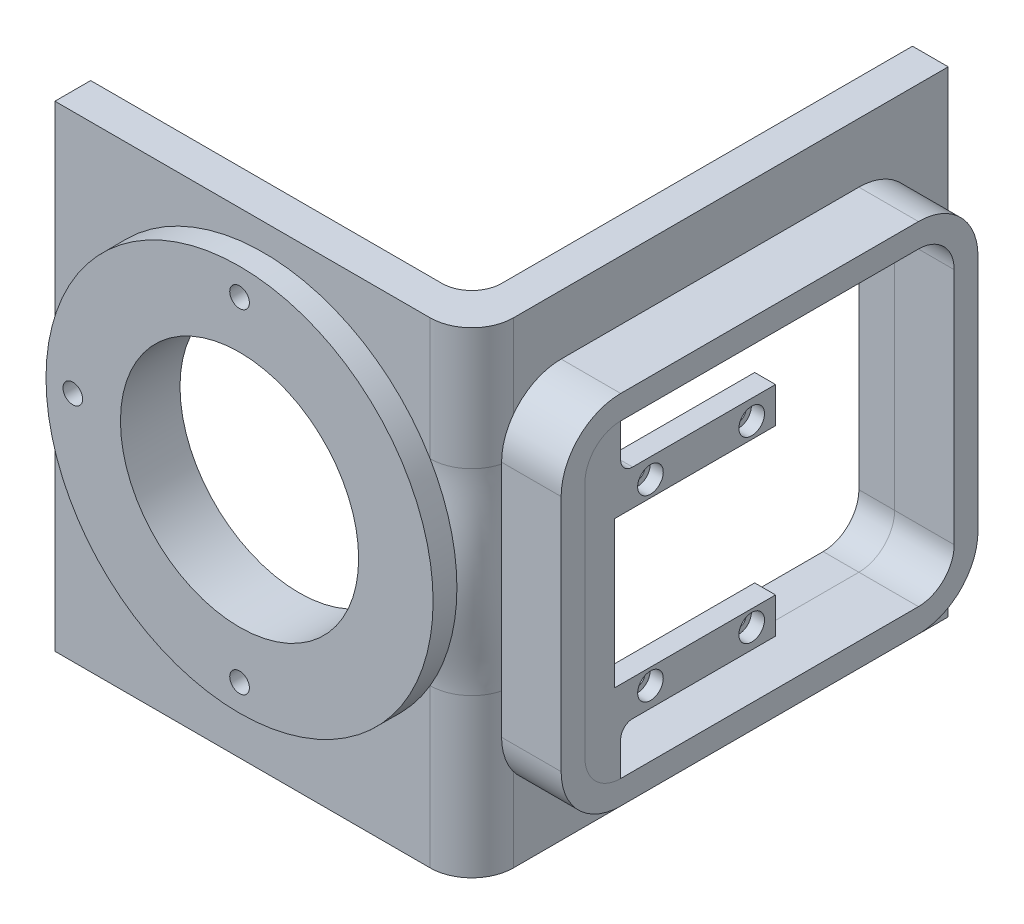
SolidWorks part; units mm, degrees
ref_plane "Front Plane" through (0, 0, 0) normal (0, 0, 1) x (1, 0, 0)
ref_plane "Top Plane" through (0, 0, 0) normal (0, 1, 0) x (1, 0, 0)
ref_plane "Right Plane" through (0, 0, 0) normal (1, 0, 0) x (0, 0, -1)
sketch "Sketch1" plane through (0, 0, 0) normal (0, 0, 1) x (1, 0, 0)
  circle A5 centre (0, 0) radius 32.5
  dimension "D1" = 65
extrude "Boss-Extrude1" add sketch "Sketch1" against normal blind 4
ref_plane "Plane1" through (45, 0, 0) normal (1, 0, 0) x (0, 0, -1)
sketch "Sketch10" plane through (0, 0, -4) normal (0, 0, -1) x (-1, 0, 0)
  line L0 (0, -3) -> (0, 0) construction
  line L1 (-35, -43) -> (35, -43)
  line L2 (-35, -43) -> (-35, 37)
  line L3 (-35, 37) -> (35, 37)
  line L4 (35, -43) -> (35, 37)
  line L5 (-35, -43) -> (35, 37) construction
  line L6 (-35, 37) -> (35, -43) construction
  point P0 (0, -3)
  dimension "D3" = 3
  dimension "D1" = 80
  dimension "D2" = 70
extrude "Boss-Extrude6" add sketch "Sketch10" along normal blind 80
sketch "Sketch2" plane through (45, 0, 0) normal (1, 0, 0) x (0, 0, -1)
  line L2 (0, -3) -> (146.6861, -3) construction
  line L3 (44, -3) -> (44, 30) construction
  line L5 (4, 37) -> (4, -43) construction
  line L6 (84, 37) -> (84, -43) construction
  line L7 (19, -33) -> (69, -33)
  line L8 (9, -23) -> (9, 17)
  line L9 (19, 27) -> (69, 27)
  line L10 (79, -23) -> (79, 17)
  line L11 (9, -33) -> (79, 27) construction
  line L12 (9, 27) -> (79, -33) construction
  arc A1 (19, -33) -> (9, -23) centre (19, -23) cw
  arc A2 (69, -33) -> (79, -23) centre (69, -23) ccw
  arc A3 (69, 27) -> (79, 17) centre (69, 17) cw
  arc A4 (9, 17) -> (19, 27) centre (19, 17) cw
  point P0 (84, -3)
  dimension "D1" = 70
  dimension "D3" = 10
  dimension "D2" = 60
extrude "Boss-Extrude2" add sketch "Sketch2" against normal up to surface (10 mm away) separate body up to face at (35, -3, -44)
sketch "Sketch11" plane through (0, 37, 0) normal (0, 1, 0) x (1, 0, 0)
  line L1 (-35, 84) -> (29, 84)
  line L2 (-35, 84) -> (-35, 10)
  line L3 (-35, 10) -> (29, 10)
  line L4 (29, 84) -> (29, 10)
  dimension "D1" = 74
  dimension "D2" = 64
extrude "Cut-Extrude5" cut sketch "Sketch11" against normal through all
sketch "Sketch4" plane through (35, 0, 0) normal (-1, 0, 0) x (0, 0, 1)
  line L8 (-69, -29) -> (-19, -29)
  line L9 (-75, 17) -> (-75, -23)
  line L10 (-19, 23) -> (-69, 23)
  line L11 (-13, -23) -> (-13, 17)
  line L12 (-69, -29) -> (-19, -29)
  line L13 (-75, 17) -> (-75, -23)
  line L14 (-19, 23) -> (-69, 23)
  line L15 (-13, -23) -> (-13, 17)
  arc A10 (-75, -23) -> (-69, -29) centre (-69, -23) ccw
  arc A11 (-69, 23) -> (-75, 17) centre (-69, 17) ccw
  arc A12 (-13, 17) -> (-19, 23) centre (-19, 17) ccw
  arc A13 (-19, -29) -> (-13, -23) centre (-19, -23) ccw
  arc A14 (-75, -23) -> (-69, -29) centre (-69, -23) ccw
  arc A15 (-69, 23) -> (-75, 17) centre (-69, 17) ccw
  arc A16 (-13, 17) -> (-19, 23) centre (-19, 17) ccw
  arc A17 (-19, -29) -> (-13, -23) centre (-19, -23) ccw
  dimension "D1" = 4
extrude "Cut-Extrude2" cut sketch "Sketch4" against normal through all contours L12 A17 L15 A16 L14 A15 L13 A14 region at (35, -3, -44)
sketch "Sketch5" plane through (45, 0, 0) normal (1, 0, 0) x (0, 0, -1)
  line L0 (48, -3) -> (13, -3) construction
  line L1 (45, 15.3) -> (45, 9.3)
  line L2 (45, 9.3) -> (18, 9.3)
  line L3 (18, 9.3) -> (18, -15.3)
  line L4 (18, -15.3) -> (45, -15.3)
  line L5 (45, -15.3) -> (45, -21.3)
  line L6 (45, -21.3) -> (19, -21.3)
  line L8 (45, 15.3) -> (19, 15.3)
  line L10 (48, -3) -> (48, -18) construction
  line L11 (48, -18) -> (41, -18) construction
  line L12 (41, -18) -> (39, -18) construction
  line L13 (39, -18) -> (24, -18) construction
  line L15 (13, 17) -> (13, -23)
  line L16 (19, 15.3) -> (19, 23)
  line L17 (19, -21.3) -> (19, -29)
  line L18 (13, -23) -> (13, 17) construction
  circle A0 centre (48, -3) radius 11 construction
  arc A1 (19, 23) -> (13, 17) centre (19, 17) ccw construction
  circle A2 centre (41, -18) radius 1.25
  arc A3 (19, 23) -> (13, 17) centre (19, 17) ccw
  circle A6 centre (24, -18) radius 1.25
  circle A7 centre (41, 12) radius 1.25
  circle A9 centre (24, 12) radius 1.25
  arc A10 (13, -23) -> (19, -29) centre (19, -23) ccw
  point P8 (18, -3)
  dimension "D1" = 22
  dimension "D6" = 2.5
  dimension "D3" = 24.6
  dimension "D4" = 15
  dimension "D5" = 7
  dimension "D7" = 17
  dimension "D9" = 6
  dimension "D10" = 5
  dimension "D12" = 3
  dimension "D2" = 30
extrude "Boss-Extrude3" add sketch "Sketch5" against normal blind 3.5
sketch "Sketch13" plane through (35, 0, 0) normal (1, 0, 0) x (0, 0, -1)
  line L4 (13, 17) -> (13, -23)
  line L5 (19, -29) -> (69, -29)
  line L6 (75, -23) -> (75, 17)
  line L7 (69, 23) -> (19, 23)
  line L8 (13, 17) -> (13, -23)
  line L9 (19, -29) -> (69, -29)
  line L10 (75, -23) -> (75, 17)
  line L11 (69, 23) -> (19, 23)
  arc A6 (19, 23) -> (13, 17) centre (19, 17) ccw
  arc A7 (13, -23) -> (19, -29) centre (19, -23) ccw
  arc A8 (69, -29) -> (75, -23) centre (69, -23) ccw
  arc A9 (75, 17) -> (69, 23) centre (69, 17) ccw
  arc A10 (19, 23) -> (13, 17) centre (19, 17) ccw
  arc A11 (13, -23) -> (19, -29) centre (19, -23) ccw
  arc A12 (69, -29) -> (75, -23) centre (69, -23) ccw
  arc A13 (75, 17) -> (69, 23) centre (69, 17) ccw
  dimension "D1" = 0
extrude "Cut-Extrude6" cut sketch "Sketch13" against normal up to surface (6 mm away) up to face at (29, -3, -47)
sketch "Sketch14" plane through (0, 0, 0) normal (0, 0, 1) x (1, 0, 0)
  circle A2 centre (0, 0) radius 28.5
  circle A3 centre (0, 0) radius 28.5
  dimension "D1" = 4
sketch "Sketch16" plane through (45, 0, 0) normal (1, 0, 0) x (0, 0, -1)
  circle A0 centre (41, -18) radius 2.15
  circle A2 centre (24, -18) radius 2.15
  circle A3 centre (24, 12) radius 2.15
  circle A5 centre (41, 12) radius 2.15
  dimension "D1" = 4.3
extrude "Cut-Extrude8" cut sketch "Sketch16" against normal blind 2.2
fillet "Fillet1" radius 7 1 edges at (35, -3, -4)
fillet "Fillet2" [suppressed] radius 10
sketch "Sketch17" plane through (0, 0, -10) normal (0, 0, -1) x (-1, 0, 0)
  line L0 (-28, 0) -> (0, 0) construction
  line L1 (0, 28) -> (0, 0) construction
  line L2 (28, 0) -> (0, 0) construction
  line L3 (0, -28) -> (0, 0) construction
  circle A0 centre (-28, 0) radius 1.65 construction
  circle A1 centre (0, 28) radius 1.65
  circle A2 centre (28, 0) radius 1.65
  circle A3 centre (0, -28) radius 1.65
  point P10 (0, 0)
  point P17 (0, 0)
  dimension "D4" = 3.3
  dimension "D3" = 28
  dimension "D1" = 4
  dimension "D2" = 4
extrude "Cut-Extrude9" cut sketch "Sketch17" against normal through all
sketch "Sketch19" plane through (29, 0, 0) normal (-1, 0, 0) x (0, 0, 1)
  line L0 (-76, 37) -> (-76, -43) construction
  line L1 (-10, 37) -> (-84, 37) construction
  line L2 (-10, -43) -> (-84, -43) construction
  line L3 (-84, -43) -> (-84, 37) construction
  line L4 (-76, 30) -> (-78, 30)
  line L5 (-76, 30) -> (-76, 25.8)
  line L6 (-76, 25.8) -> (-78, 25.8)
  line L7 (-78, 30) -> (-78, 25.8)
  line L8 (-76, -31.8) -> (-78, -31.8)
  line L9 (-76, -31.8) -> (-76, -36)
  line L10 (-76, -36) -> (-78, -36)
  line L11 (-78, -31.8) -> (-78, -36)
  line L12 (-76, -3) -> (-84, -3) construction
  dimension "D1" = 8
  dimension "D2" = 7
  dimension "D3" = 2
  dimension "D4" = 4.2
extrude "Cut-Extrude10" cut sketch "Sketch19" along direction (1, 0, 0) on the side against the normal blind 4.8
sketch "Sketch21" plane through (0, 0, -10) normal (0, 0, -1) x (-1, 0, 0)
  line L0 (27, 37) -> (27, -43) construction
  line L1 (29, 30) -> (27, 30)
  line L2 (29, 30) -> (29, 25.8)
  line L3 (29, 25.8) -> (27, 25.8)
  line L4 (27, 30) -> (27, 25.8)
  line L5 (29, -31.8) -> (27, -31.8)
  line L6 (29, -31.8) -> (29, -36)
  line L7 (29, -36) -> (27, -36)
  line L8 (27, -31.8) -> (27, -36)
  line L9 (27, -3) -> (35, -3) construction
  line L10 (35, -43) -> (35, 37) construction
  line L11 (35, 37) -> (-29, 37) construction
  point P12 (35, -3)
  point P15 (24.1104, 37)
  dimension "D1" = 2
  dimension "D2" = 4.2
  dimension "D3" = 7
  dimension "D4" = 8
extrude "Cut-Extrude11" cut sketch "Sketch21" against normal blind 4.8
sketch "Sketch22" plane through (0, 0, -84) normal (0, 0, -1) x (-1, 0, 0)
  line L0 (-29, 30) -> (-33.8, 25.8) construction
  line L1 (-29, -31.8) -> (-33.8, -36) construction
  line L4 (-29, 25.8) -> (-29, 30)
  line L5 (-29, 30) -> (-33.8, 30)
  line L6 (-33.8, 30) -> (-33.8, 25.8)
  line L7 (-33.8, 25.8) -> (-29, 25.8)
  line L8 (-29, 25.8) -> (-29, 30) construction
  line L9 (-29, 30) -> (-33.8, 30) construction
  line L11 (-33.8, 25.8) -> (-29, 25.8) construction
  line L12 (-29, -36) -> (-29, -31.8)
  line L13 (-29, -31.8) -> (-33.8, -31.8)
  line L14 (-33.8, -31.8) -> (-33.8, -36)
  line L15 (-33.8, -36) -> (-29, -36)
  line L16 (-29, -36) -> (-29, -31.8) construction
  line L17 (-29, -31.8) -> (-33.8, -31.8) construction
  line L19 (-33.8, -36) -> (-29, -36) construction
  line L22 (-33.8, 30) -> (-33.8, 25.8)
  line L23 (-33.8, -31.8) -> (-33.8, -36)
  circle A0 centre (-31.4, 27.9) radius 1.15
  circle A1 centre (-31.4, -33.9) radius 1.15
  point P12 (-32.4, -33.9)
  point P13 (-32.4, 27.9)
  dimension "D3" = 2.3
  dimension "D1" = 0
  dimension "D2" = 0
extrude "Cut-Extrude12" cut sketch "Sketch22" against normal up to surface (6 mm away) contours A0 | A1 region at (31.4, 27.9, -84) region at (31.4, -33.9, -84) up to face at (31.4, 27.9, -78)
sketch "Sketch23" plane through (-35, 0, 0) normal (-1, 0, 0) x (0, 0, 1)
  line L0 (-10, -36) -> (-5.2, -31.8) construction
  line L1 (-10, 25.8) -> (-5.2, 30) construction
  line L4 (-10, -31.8) -> (-10, -36)
  line L5 (-10, -36) -> (-5.2, -36)
  line L6 (-5.2, -36) -> (-5.2, -31.8)
  line L7 (-5.2, -31.8) -> (-10, -31.8)
  line L8 (-10, -31.8) -> (-10, -36) construction
  line L9 (-10, -36) -> (-5.2, -36) construction
  line L10 (-5.2, -36) -> (-5.2, -31.8) construction
  line L11 (-5.2, -31.8) -> (-10, -31.8) construction
  line L12 (-10, 30) -> (-10, 25.8)
  line L13 (-10, 25.8) -> (-5.2, 25.8)
  line L14 (-5.2, 25.8) -> (-5.2, 30)
  line L15 (-5.2, 30) -> (-10, 30)
  line L16 (-10, 30) -> (-10, 25.8) construction
  line L17 (-10, 25.8) -> (-5.2, 25.8) construction
  line L18 (-5.2, 25.8) -> (-5.2, 30) construction
  line L19 (-5.2, 30) -> (-10, 30) construction
  circle A0 centre (-7.6, -33.9) radius 1.15
  circle A1 centre (-7.6, 27.9) radius 1.15
  dimension "D3" = 2.3
  dimension "D1" = 0
  dimension "D2" = 0
extrude "Cut-Extrude13" cut sketch "Sketch23" against normal up to surface (6 mm away) up to face at (-29, -33.9, -7.6)
sketch "Sketch24" plane through (0, 0, -10) normal (0, 0, -1) x (-1, 0, 0)
  circle A0 centre (0, 0) radius 20
  dimension "D1" = 40
extrude "Cut-Extrude14" cut sketch "Sketch24" against normal up to surface (10 mm away) up to face at (-1.65, 28, 0)
fillet "Fillet4" radius 5 1 edges at (29, -3, -10)
fillet "Fillet5" radius 2 2 edges at (43.25, -21.3, -19) (43.25, 15.3, -19)
